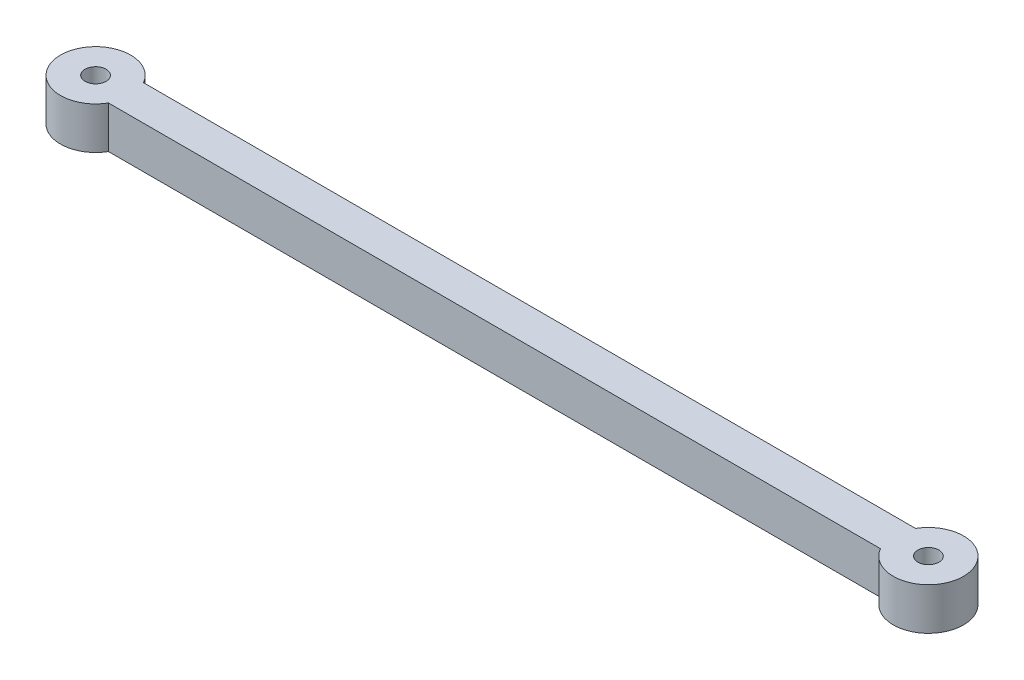
SolidWorks part; units mm, degrees
ref_plane "Front Plane" through (0, 0, 0) normal (0, 0, 1) x (1, 0, 0)
ref_plane "Top Plane" through (0, 0, 0) normal (0, 1, 0) x (1, 0, 0)
ref_plane "Right Plane" through (0, 0, 0) normal (1, 0, 0) x (0, 0, -1)
sketch "Sketch1" plane through (0, 0, 0) normal (0, 1, 0) x (1, 0, 0)
  line L0 (-55, 2.5) -> (55, 2.5)
  line L1 (-55, -2.5) -> (55, -2.5)
  line L2 (-55, 0) -> (55, 0) construction
  arc A1 (-55, 2.5) -> (-55, -2.5) centre (-59.3301, 0) ccw
  arc A2 (55, 2.5) -> (55, -2.5) centre (59.3301, 0) cw
  dimension "D2" = 55
  dimension "D3" = 5
  dimension "D7" = 5
  dimension "D1" = 5
  dimension "D4" = 110
  dimension "D5" = 110
  dimension "D6" = 2.5
extrude "Boss-Extrude1" add sketch "Sketch1" along normal blind 6
sketch "Sketch2" plane through (0, 6, 0) normal (0, 1, 0) x (1, 0, 0)
  circle A0 centre (-59.3301, 0) radius 1.5
  circle A1 centre (59.3301, 0) radius 1.5
  dimension "D1" = 3
  dimension "D2" = 3
extrude "Cut-Extrude1" cut sketch "Sketch2" against normal through all
